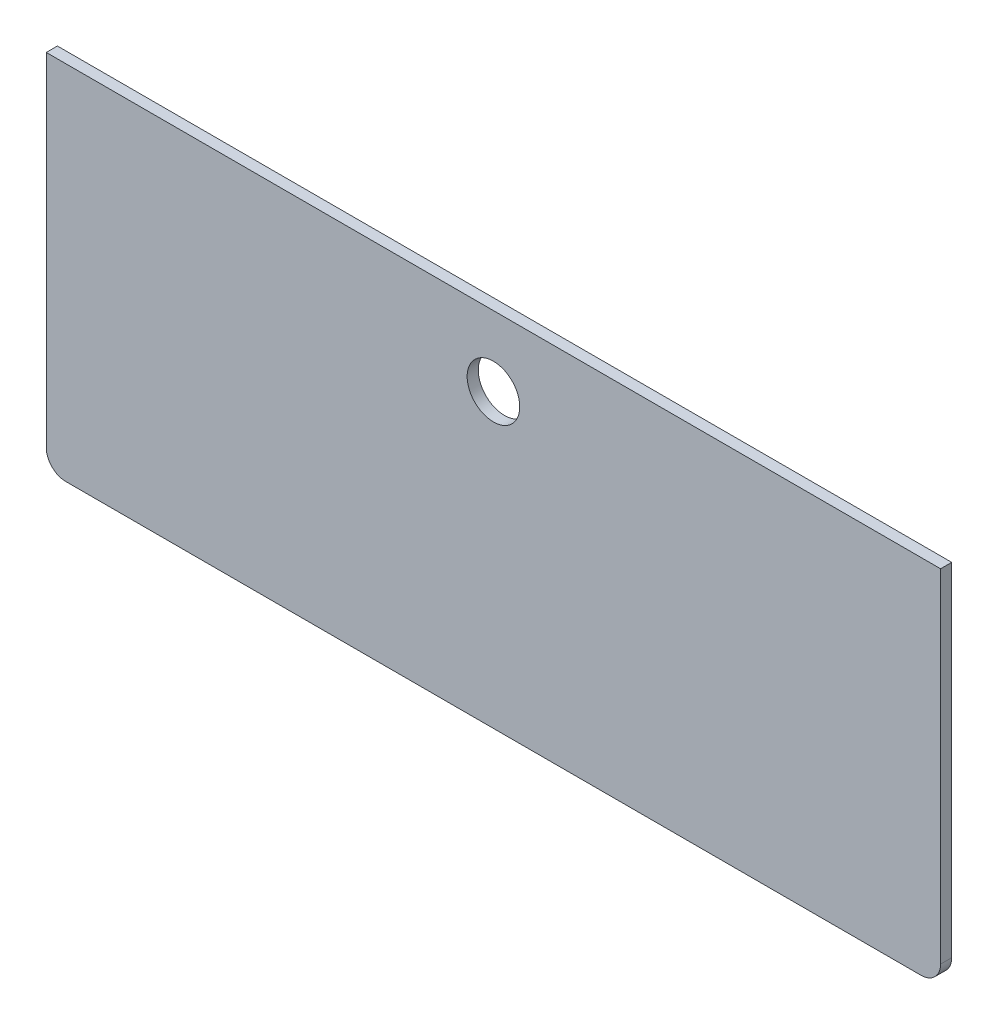
SolidWorks part; units mm, degrees
material "5052-H32"
ref_plane "Front Plane" through (0, 0, 0) normal (0, 0, 1) x (1, 0, 0)
ref_plane "Top Plane" through (0, 0, 0) normal (0, 1, 0) x (1, 0, 0)
ref_plane "Right Plane" through (0, 0, 0) normal (1, 0, 0) x (0, 0, -1)
sketch "Sketch1" plane through (0, 0, 0) normal (0, 0, 1) x (1, 0, 0)
  line L0 (-151.7654, 27.1868) -> (-151.7654, -75.9882)
  line L1 (-151.7654, -75.9882) -> (103.2346, -75.9882)
  line L2 (103.2346, -75.9882) -> (103.2346, 27.1868)
  line L3 (103.2346, 27.1868) -> (-151.7654, 27.1868)
  line L4 (-24.2654, 27.1868) -> (-24.2654, 7.1868) construction
  circle A0 centre (-24.2654, 7.1868) radius 7.5
  dimension "D4" = 15
  dimension "D1" = 103.175
  dimension "D2" = 255
  dimension "D3" = 20
extrude "Boss-Extrude1" add sketch "Sketch1" along normal blind 3.175
fillet "Fillet1" radius 5.5562 2 edges at (-151.7654, -75.9882, 1.5875) (103.2346, -75.9882, 1.5875)
equation "\"L\"= 400"
equation "\"W\"= 255"
equation "\"H\"= 110"
equation "\"Compartment Width\"= 80"
equation "\"T\"= 4.7625 * 2 / 3"
equation "\"Inside Fillet Radius\"= 5.55625"
equation "\"D1@Boss-Extrude1\"=\"T\""
equation "\"D1@Fillet1\"=\"Inside Fillet Radius\""
equation "\"Hole\"=15"
equation "\"D4@Sketch1\"=\"Hole\""
equation "\"D2@Sketch1\"=\"W\""
equation "\"D1@Sketch1\"=\"H\"+\"T\"-10"
equation "\"Offset\"= 30"
equation "\"Wheel to Wall\"= 43"
